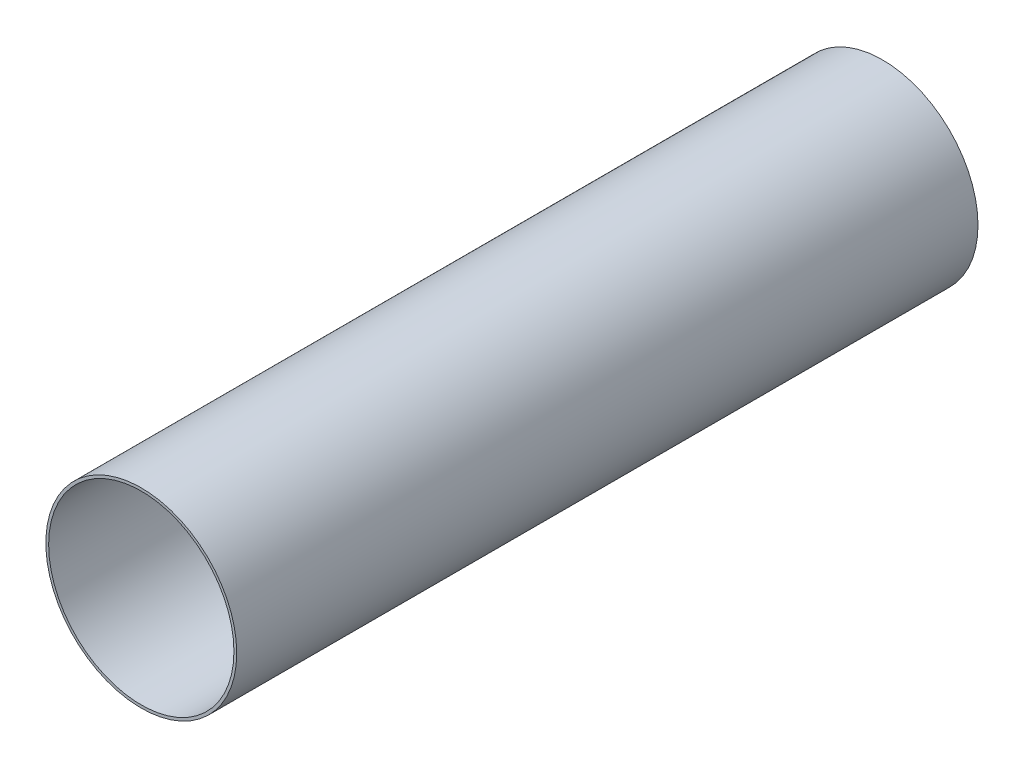
SolidWorks part; units mm, degrees
ref_plane "Front Plane" through (0, 0, 0) normal (0, 0, 1) x (1, 0, 0)
ref_plane "Top Plane" through (0, 0, 0) normal (0, 1, 0) x (1, 0, 0)
ref_plane "Right Plane" through (0, 0, 0) normal (1, 0, 0) x (0, 0, -1)
sketch "Sketch1" plane through (0, 0, 0) normal (0, 0, 1) x (1, 0, 0)
  circle A0 centre (0, 0) radius 65.405
  circle A1 centre (0, 0) radius 63.5
  dimension "D1" = 127
  dimension "D2" = 130.81
extrude "Boss-Extrude1" add sketch "Sketch1" along normal mid plane 508
equation "\"AIRFRAME_OD\"= 5.15in"
equation "\"AIRFRAME_ID\"= 5.00in"
equation "\"FLAT_T\"= 0.125in"
equation "\"NOSE_EXP_L\"= 27in"
equation "\"NOSE_SHOULDER_L\"= 5in"
equation "\"MAIN_L\"= 30in"
equation "\"RECO_COUP_L\"= 10in"
equation "\"RECO_SWITCH_L\"= 2in"
equation "\"DROGUE_L\"= 20in"
equation "\"ATS_FORE_COUP_L\"= 5.5in"
equation "\"ATS_AFT_COUP_L\"= 4.5in"
equation "\"LOWER_L\"= 30in"
equation "\"FIN_N\"= 4"
equation "\"CR_AFT_X\"= 0.5in"
equation "\"CR_FORE_X\"= 9.25in"
equation "\"D1@Sketch1\"=\"AIRFRAME_ID\""
equation "\"D2@Sketch1\"=\"AIRFRAME_OD\""
equation "\"D1@Boss-Extrude1\"=\"DROGUE_L\""
equation "\"FIN_ROOT\"= 5in"
equation "\"FIN_X\"= 0.75in"
equation "\"MOTOR_OD\"= 3.091in"
equation "\"MOTOR_ID\"= 3.00in"
equation "\"COUPLER_OD\"= 4.998in"
equation "\"COUPLER_ID\"= 4.88in"
equation "\"RECO_ROD_X\"= 3.5in"
equation "\"ATS_ROD_X\"= 3in"
equation "\"MOTOR_L\"= 14in"
equation "\"MOTOR_LOWER_X\"= 2in"
